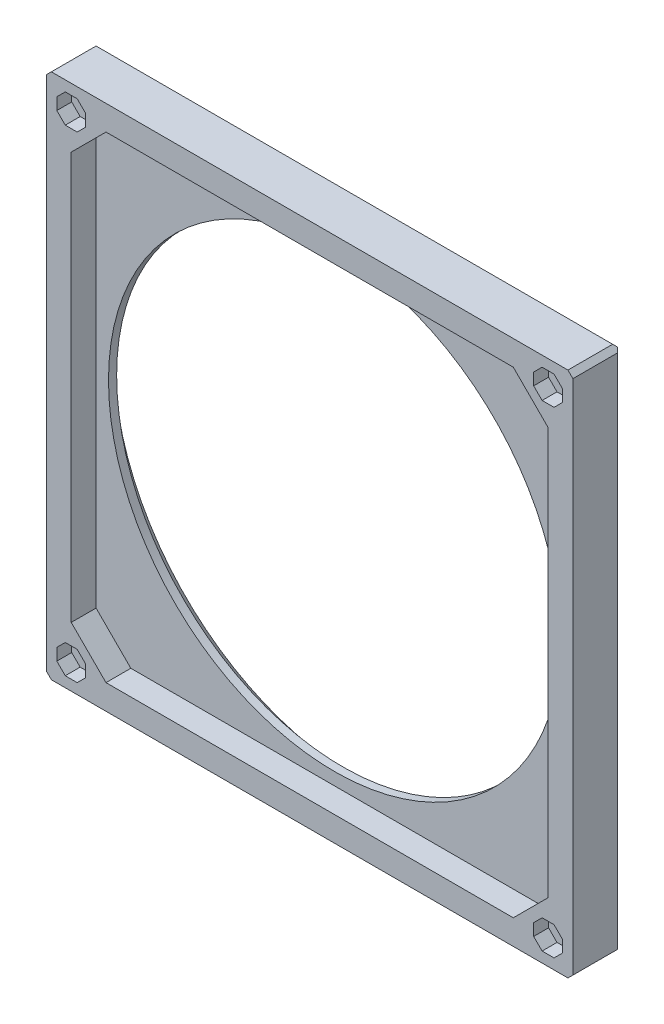
SolidWorks part; units mm, degrees
ref_plane "Front Plane" through (0, 0, 0) normal (0, 0, 1) x (1, 0, 0)
ref_plane "Top Plane" through (0, 0, 0) normal (0, 1, 0) x (1, 0, 0)
ref_plane "Right Plane" through (0, 0, 0) normal (1, 0, 0) x (0, 0, -1)
sketch "Sketch1 larger dia" plane through (0, 0, 0) normal (0, 0, 1) x (1, 0, 0)
  line L0 (-41, 48) -> (41, 48)
  line L1 (-53, 53) -> (53, 53)
  line L2 (-53, 53) -> (-53, -53)
  line L3 (-53, -53) -> (53, -53)
  line L4 (53, 53) -> (53, -53)
  line L5 (41, 48) -> (48, 41)
  line L6 (48, 41) -> (48, -41)
  line L7 (48, -41) -> (41, -48)
  line L8 (41, -48) -> (-41, -48)
  line L9 (-41, -48) -> (-48, -41)
  line L10 (-48, -41) -> (-48, 41)
  line L11 (-48, 41) -> (-41, 48)
  dimension "D2" = 12
  dimension "D3" = 5
  dimension "D4" = 5
  dimension "D5" = 5
  dimension "D6" = 5
  dimension "D8" = 12
  dimension "D9" = 12
  dimension "D10" = 12
  dimension "D11" = 12
  dimension "D12" = 12
sketch "Sketch3 holes" plane through (0, 0, 0) normal (0, 0, 1) x (1, 0, 0)
  line L1 (-53, 53) -> (53, 53) construction
  line L2 (-53, 53) -> (-53, -53) construction
  line L3 (-53, -53) -> (53, -53) construction
  line L4 (53, 53) -> (53, -53) construction
  circle A0 centre (-48, 48) radius 1.5
  circle A1 centre (48, 48) radius 1.5
  circle A2 centre (-48, -48) radius 1.5
  circle A3 centre (48, -48) radius 1.5
  dimension "D1" = 5
  dimension "D3" = 3
  dimension "D6" = 3
  dimension "D9" = 3
  dimension "D12" = 3
  dimension "D2" = 5
  dimension "D4" = 5
  dimension "D5" = 5
  dimension "D7" = 5
  dimension "D8" = 5
  dimension "D10" = 5
  dimension "D11" = 5
sketch "Sketch4 ring" plane through (0, 0, 0) normal (0, 0, 1) x (1, 0, 0)
  circle A0 centre (0, 0) radius 47.75
  circle A1 centre (0, 0) radius 45.5
  dimension "D1" = 95.5
  dimension "D2" = 91
extrude "Boss-Extrude1" add sketch "Sketch1 larger dia" along normal blind 5
sketch "Sketch5 smaller dia" plane through (0, 0, 0) normal (0, 0, -1) x (-1, 0, 0)
  line L1 (-53, 53) -> (53, 53)
  line L2 (-53, 53) -> (-53, -53)
  line L3 (-53, -53) -> (53, -53)
  line L4 (53, 53) -> (53, -53)
  circle A0 centre (0, 0) radius 45.5
  dimension "D1" = 91
extrude "Boss-Extrude2" add sketch "Sketch5 smaller dia" along normal blind 5
sketch "Sketch1" plane through (0, 0, 5) normal (0, 0, 1) x (1, 0, 0)
  line L0 (0, 53) -> (0, -53) construction
  line L1 (-53, 53) -> (53, 53) construction
  line L2 (-53, 53) -> (-53, -53) construction
  line L3 (-53, -53) -> (53, -53) construction
  line L4 (53, 53) -> (53, -53) construction
  line L5 (-45.1, 46.7988) -> (-45.1, 49.2012)
  line L6 (-45.1, 49.2012) -> (-46.7988, 50.9)
  line L7 (-46.7988, 50.9) -> (-49.2012, 50.9)
  line L8 (-49.2012, 50.9) -> (-50.9, 49.2012)
  line L9 (-50.9, 49.2012) -> (-50.9, 46.7988)
  line L10 (-50.9, 46.7988) -> (-49.2012, 45.1)
  line L11 (-49.2012, 45.1) -> (-46.7988, 45.1)
  line L12 (-46.7988, 45.1) -> (-45.1, 46.7988)
  line L13 (-53, 0) -> (53, 0) construction
  line L14 (-46.7988, -45.1) -> (-45.1, -46.7988)
  line L15 (-49.2012, -45.1) -> (-46.7988, -45.1)
  line L16 (-50.9, -46.7988) -> (-49.2012, -45.1)
  line L17 (-50.9, -49.2012) -> (-50.9, -46.7988)
  line L18 (-49.2012, -50.9) -> (-50.9, -49.2012)
  line L19 (-46.7988, -50.9) -> (-49.2012, -50.9)
  line L20 (-45.1, -49.2012) -> (-46.7988, -50.9)
  line L21 (-45.1, -46.7988) -> (-45.1, -49.2012)
  line L22 (46.7988, 45.1) -> (45.1, 46.7988)
  line L23 (49.2012, 45.1) -> (46.7988, 45.1)
  line L24 (50.9, 46.7988) -> (49.2012, 45.1)
  line L25 (50.9, 49.2012) -> (50.9, 46.7988)
  line L26 (49.2012, 50.9) -> (50.9, 49.2012)
  line L27 (46.7988, 50.9) -> (49.2012, 50.9)
  line L28 (45.1, 49.2012) -> (46.7988, 50.9)
  line L29 (45.1, 46.7988) -> (45.1, 49.2012)
  line L30 (45.1, -46.7988) -> (45.1, -49.2012)
  line L31 (45.1, -49.2012) -> (46.7988, -50.9)
  line L32 (46.7988, -50.9) -> (49.2012, -50.9)
  line L33 (49.2012, -50.9) -> (50.9, -49.2012)
  line L34 (50.9, -49.2012) -> (50.9, -46.7988)
  line L35 (50.9, -46.7988) -> (49.2012, -45.1)
  line L36 (49.2012, -45.1) -> (46.7988, -45.1)
  line L37 (46.7988, -45.1) -> (45.1, -46.7988)
  circle A4 centre (-48, 48) radius 2.9 construction
  circle A5 centre (-48, -48) radius 2.9 construction
  circle A6 centre (48, 48) radius 2.9 construction
  circle A7 centre (48, -48) radius 2.9 construction
  dimension "D3" = 5
  dimension "D13" = 5.8
  dimension "D2" = 5
  dimension "D4" = 106
extrude "Cut-Extrude1" cut sketch "Sketch1" against normal blind 3
chamfer "Chamfer1" distance 4 angle 40 1 edges at (-45.5, 0, -5) first distance on face at (0, 0, -5)
chamfer "Chamfer2" distance 1 4 edges at (0, -53, -5) (53, 0, -5) (0, 53, -5) (-53, 0, -5)
chamfer "Chamfer3" distance 1 angle 45 4 edges at (53, -53, 0.5) (-53, -53, 0.5) (-53, 53, 0.5) (53, 53, 0.5)
